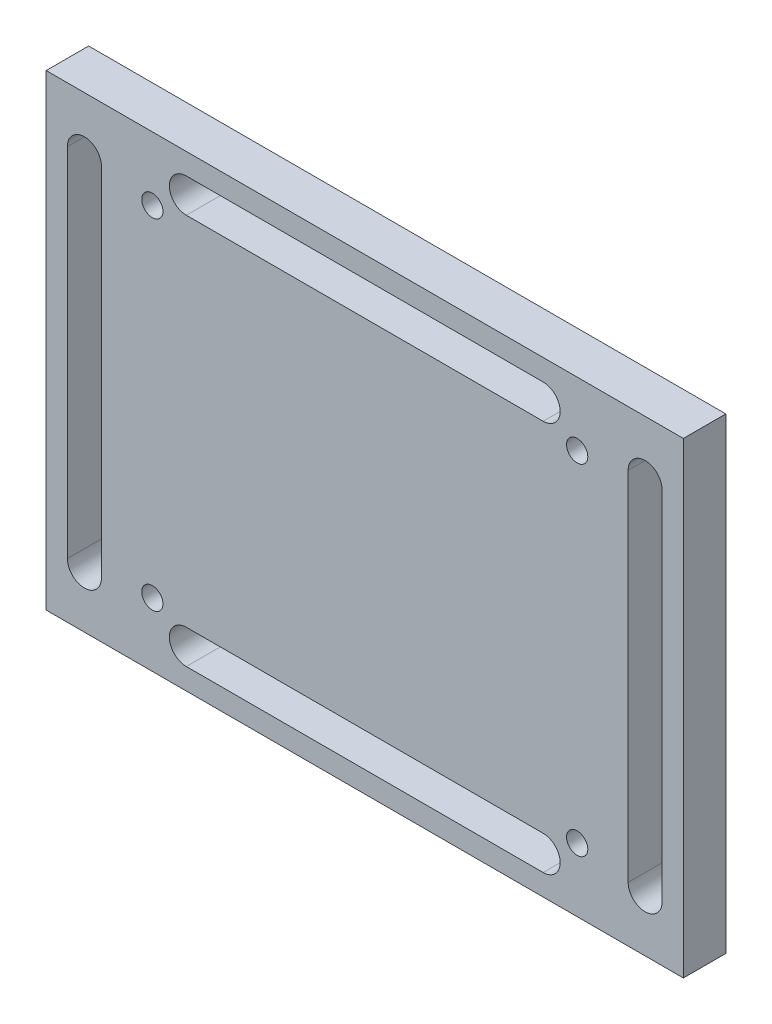
SolidWorks part; units mm, degrees
ref_plane "Front Plane" through (0, 0, 0) normal (0, 0, 1) x (1, 0, 0)
ref_plane "Top Plane" through (0, 0, 0) normal (0, 1, 0) x (1, 0, 0)
ref_plane "Right Plane" through (0, 0, 0) normal (1, 0, 0) x (0, 0, -1)
sketch "Sketch1" plane through (0, 0, 0) normal (0, 0, 1) x (1, 0, 0)
  line L0 (-21, 23) -> (21, 23) construction
  line L1 (-21, 25) -> (21, 25)
  line L2 (-21, 21) -> (21, 21)
  line L3 (-1000, 0) -> (49000, 0) construction
  line L4 (-37.5, 27.5) -> (-37.5, -27.5)
  line L5 (-37.5, -27.5) -> (37.5, -27.5)
  line L6 (37.5, -27.5) -> (37.5, 27.5)
  line L7 (37.5, 27.5) -> (-37.5, 27.5)
  line L8 (-37.5, 27.5) -> (-37.5, -27.5)
  line L9 (-37.5, -27.5) -> (37.5, -27.5)
  line L10 (37.5, -27.5) -> (37.5, 27.5)
  line L11 (37.5, 27.5) -> (-37.5, 27.5)
  line L12 (-21, -23) -> (21, -23) construction
  line L13 (-21, -25) -> (21, -25)
  line L14 (-21, -21) -> (21, -21)
  line L15 (0, -1000) -> (0, 49000) construction
  line L16 (-33, 21) -> (-33, -21) construction
  line L17 (-31, 21) -> (-31, -21)
  line L18 (-35, 21) -> (-35, -21)
  line L19 (33, 21) -> (33, -21) construction
  line L20 (31, 21) -> (31, -21)
  line L21 (35, 21) -> (35, -21)
  circle A0 centre (-25, 20) radius 1.25
  circle A1 centre (25, 20) radius 1.25
  circle A2 centre (25, -20) radius 1.25
  circle A3 centre (-25, -20) radius 1.25
  arc A4 (-21, 25) -> (-21, 21) centre (-21, 23) ccw
  arc A5 (21, 21) -> (21, 25) centre (21, 23) ccw
  arc A6 (-21, -25) -> (-21, -21) centre (-21, -23) cw
  arc A7 (21, -21) -> (21, -25) centre (21, -23) cw
  arc A8 (-31, 21) -> (-35, 21) centre (-33, 21) ccw
  arc A9 (-35, -21) -> (-31, -21) centre (-33, -21) ccw
  arc A10 (31, 21) -> (35, 21) centre (33, 21) cw
  arc A11 (35, -21) -> (31, -21) centre (33, -21) cw
  point P18 (0, 23)
  point P29 (0, -23)
  point P38 (-33, 0)
  point P43 (0, 0)
  point P44 (0, 0)
  point P47 (33, 0)
  dimension "D2" = 2.5
  dimension "D3" = 42
  dimension "D4" = 4
  dimension "D5" = 4.5
  dimension "D7" = 42
  dimension "D8" = 4
  dimension "D9" = 4.5
  dimension "D1" = 0
extrude "Boss-Extrude1" add sketch "Sketch1" along normal blind 5
